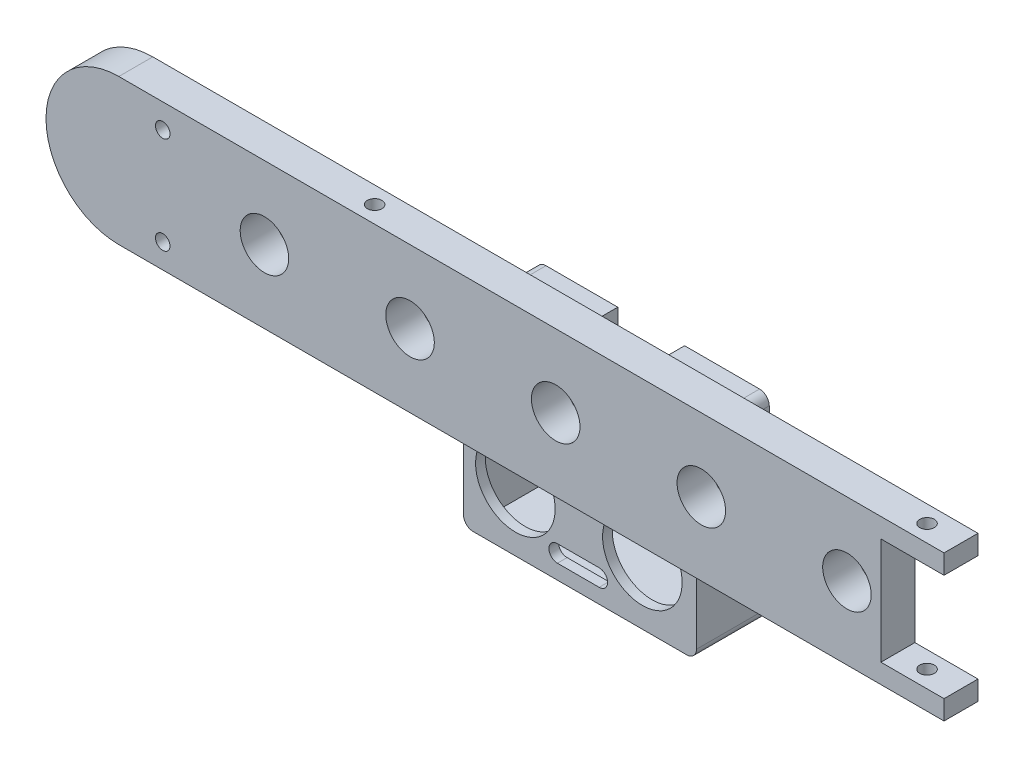
SolidWorks part; units mm, degrees
ref_plane "Front Plane" through (0, 0, 0) normal (0, 0, 1) x (1, 0, 0)
ref_plane "Top Plane" through (0, 0, 0) normal (0, 1, 0) x (1, 0, 0)
ref_plane "Right Plane" through (0, 0, 0) normal (1, 0, 0) x (0, 0, -1)
sketch "Sketch1" plane through (0, 0, 0) normal (0, 0, 1) x (1, 0, 0)
  line L0 (-200, 0) -> (50, 0)
  line L1 (50, -30) -> (-200, -30)
  arc A0 (50, 0) -> (50, -30) centre (50, -15) cw
  arc A1 (-200, -30) -> (-200, 0) centre (-200, -15) cw
  point P7 (-75, 0)
  dimension "D3" = 50
  dimension "D1" = 125
  dimension "D2" = 30
extrude "Boss-Extrude1" add sketch "Sketch1" along normal blind 7
sketch "Sketch2" plane through (0, 0, 7) normal (0, 0, 1) x (1, 0, 0)
  line L2 (50, 0) -> (-200, 0) construction
  circle A0 centre (-185, -15) radius 5
  arc A6 (-200, 0) -> (-200, -30) centre (-200, -15) ccw construction
  point P22 (-215, -15)
  dimension "D1" = 10
  dimension "D3" = 15
  dimension "D2" = 30
extrude "Cut-Extrude1" cut sketch "Sketch2" against normal blind 7
sketch "Sketch5" plane through (0, 0, 0) normal (0, 1, 0) x (1, 0, 0)
  line L1 (-318.748, 64.8797) -> (45.4135, 64.8797) construction
  line L2 (-318.748, 64.8797) -> (-318.748, -30.5338) construction
  line L3 (-318.748, -30.5338) -> (45.4135, -30.5338) construction
  line L4 (45.4135, 64.8797) -> (45.4135, -30.5338) construction
  line L5 (-318.748, 64.8797) -> (45.4135, -30.5338) construction
  line L6 (-318.748, -30.5338) -> (45.4135, 64.8797) construction
  point P0 (-136.6672, 17.1729)
pattern_linear "LPattern1" count 7 spacing 30 along (1, 0, 0) of "Cut-Extrude1"
sketch "Sketch6" plane through (0, 0, 0) normal (0, 0, -1) x (-1, 0, 0)
  circle A0 centre (-50, -15) radius 5
  dimension "D1" = 10
extrude "Cut-Extrude2" cut sketch "Sketch6" against normal blind 10
sketch "Sketch9" plane through (0, 0, 0) normal (0, 0, -1) x (-1, 0, 0)
  line L0 (-50, -15) -> (-29.5, -15)
  line L1 (-29.5, -6.25) -> (-29.5, -23.75)
  circle A0 centre (-29.5, -6.25) radius 1.5
  circle A1 centre (-29.5, -23.75) radius 1.5
  point P6 (-29.5, -15)
  dimension "D3" = 3
  dimension "D4" = 3
  dimension "D1" = 20.5
  dimension "D2" = 17.5
extrude "Cut-Extrude4" cut sketch "Sketch9" against normal up to next contours A1 | A0
sketch "Sketch15" plane through (0, 0, 0) normal (0, 1, 0) x (1, 0, 0)
  line L0 (-200, -7) -> (-200, 0) construction
  line L1 (50, -7) -> (50, 0) construction
  circle A0 centre (-195.8, -3.5) radius 1.5
  circle A1 centre (45.8, -3.5) radius 2.5
  point P7 (-200, -3.5)
  point P12 (50, -3.5)
  dimension "D2" = 3
  dimension "D3" = 5
  dimension "D1" = 4.2
  dimension "D4" = 4.2
extrude "Cut-Extrude9" cut sketch "Sketch15" against normal up to next
sketch "Sketch16" plane through (0, 0, 0) normal (0, 0, -1) x (-1, 0, 0)
  line L0 (153.0436, -46.9176) -> (161.6481, -46.9176) construction
  line L1 (133, -51.6913) -> (181, -51.6913)
  line L2 (133, -51.6913) -> (133, -11.7609)
  line L3 (133, -11.7609) -> (181, -11.7609)
  line L4 (181, -51.6913) -> (181, -11.7609)
  line L9 (153.0436, -45.1752) -> (161.6481, -45.1752)
  line L10 (153.0436, -48.6599) -> (161.6481, -48.6599)
  circle A0 centre (144.1458, -39.2434) radius 8.2
  circle A1 centre (170.3064, -39.2434) radius 8.2
  arc A2 (153.0436, -45.1752) -> (153.0436, -48.6599) centre (153.0436, -46.9176) ccw
  arc A3 (161.6481, -48.6599) -> (161.6481, -45.1752) centre (161.6481, -46.9176) ccw
  circle A4 centre (-50, -15) radius 5 construction
  point P17 (157.3458, -46.9176)
  line M24 (-50, -30) -> (200, -30)
  dimension "D3" = 16.4
  dimension "D4" = 16.4
  dimension "D9" = 11.1458
  dimension "D6" = 8.8978
  dimension "D1" = 48
  dimension "D2" = 26.1606
  dimension "D5" = 8.6044
  dimension "D7" = 11.1458
  dimension "D8" = 11.75
  dimension "D10" = 183
extrude "Boss-Extrude2" add sketch "Sketch16" along normal blind 15 contours A0 M24 | A1 M24 | L10 A3 L9 A2 | L4 L3 L2 L1 region at (-157.3458, -46.9176, 0) region at (-144.1458, -39.2434, 0) region at (-170.3064, -39.2434, 0)
sketch "Sketch17" plane through (0, 0, -15) normal (0, 0, -1) x (-1, 0, 0)
  line L0 (133.75, -20.9008) -> (179.5838, -20.9008)
  line L1 (133.75, -20.9008) -> (133.75, -51.0259)
  line L2 (133.75, -51.0259) -> (179.5838, -51.0259)
  line L3 (179.5838, -20.9008) -> (179.5838, -51.0259)
  line L4 (150.4449, -11.7609) -> (164.2082, -11.7609)
  line L5 (150.4449, -11.7609) -> (150.4449, -20.9835)
  line L6 (150.4449, -20.9835) -> (164.2082, -20.9835)
  line L7 (164.2082, -11.7609) -> (164.2082, -20.9835)
  line L8 (133, -11.7609) -> (181, -11.7609) construction
  circle A0 centre (-50, -15) radius 5 construction
  dimension "D1" = 45.8338
  dimension "D2" = 13.7633
  dimension "D3" = 45.8338
  dimension "D4" = 30.1251
  dimension "D5" = 0
  dimension "D6" = 183.75
  dimension "D7" = 16.6949
extrude "Cut-Extrude15" cut sketch "Sketch17" against normal blind 13 contours L0 L3 L2 L1 | L4 L7 L6 L5
sketch "Sketch18" plane through (0, 0, 7) normal (0, 0, 1) x (1, 0, 0)
  line L1 (65, 42.8797) -> (-75, 42.8797)
  line L2 (65, 42.8797) -> (65, -72.9532)
  line L3 (65, -72.9532) -> (-75, -72.9532)
  line L4 (-75, 42.8797) -> (-75, -72.9532)
  dimension "D1" = 140
extrude "Cut-Extrude16" cut sketch "Sketch18" against normal up to next
fillet "Fillet1" radius 2 4 edges at (-181, -11.7609, -7.5) (-133, -11.7609, -7.5) (-133, -51.6913, -7.5) (-181, -51.6913, -7.5)
sketch "Sketch24" plane through (0, 0, 0) normal (0, 0, -1) x (-1, 0, 0)
  line L1 (200, 0) -> (245, 0)
  line L2 (200, 0) -> (200, -30)
  line L3 (200, -30) -> (245, -30)
  line L4 (245, 0) -> (245, -30)
  arc A0 (245, 0) -> (245, -30) centre (245, -15) cw
  arc M13 (200, -30) -> (200, 0) centre (200, -15) ccw
  dimension "D1" = 45
extrude "Boss-Extrude4" add sketch "Sketch24" against normal blind 7 contours A0 L4 | L4 L1 L3 M13 region at (-228.2218, -15, 0) region at (-251.3662, -15, 0)
sketch "Sketch25" plane through (0, 0, 0) normal (0, 0, -1) x (-1, 0, 0)
  line L0 (235.95, 0) -> (235.95, -30)
  line L1 (75, 0) -> (245, 0) construction
  circle A0 centre (235.95, -25) radius 1.5
  circle A1 centre (235.95, -5) radius 1.5
  arc A2 (245, -30) -> (245, 0) centre (245, -15) ccw construction
  point P9 (260, -15)
  point P10 (235.95, 0)
  dimension "D3" = 3
  dimension "D4" = 3
  dimension "D1" = 30
  dimension "D2" = 20
  dimension "D5" = 5
  dimension "D6" = 24.05
extrude "Cut-Extrude17" cut sketch "Sketch25" against normal blind 10 contours L0 A0 | L0 A0 | L0 A1 | L0 A1 region at (-236.5866, -5, 0) region at (-236.5866, -25, 0) region at (-235.3134, -25, 0) region at (-235.3134, -5, 0)
sketch "Sketch27" plane through (-75, 0, 0) normal (1, 0, 0) x (0, 0, -1)
  line L8 (-7, 0) -> (-7, -30) construction
  line L9 (-7, -4) -> (0, -4)
  line L10 (-7, -4) -> (-7, -26)
  line L11 (-7, -26) -> (0, -26)
  line L12 (0, -4) -> (0, -26)
  line L13 (0, 0) -> (0, -30) construction
  line L14 (-7, -30) -> (0, -30) construction
  line L15 (0, 0) -> (-7, 0) construction
  dimension "D1" = 4
  dimension "D2" = 4
extrude "Cut-Extrude18" cut sketch "Sketch27" against normal blind 13
sketch "Sketch28" plane through (0, 0, 0) normal (0, 1, 0) x (1, 0, 0)
  line L0 (-75, 0) -> (-75, -7) construction
  circle A0 centre (-82, -3.5) radius 1.5
  dimension "D2" = 3
  dimension "D1" = 7
extrude "Cut-Extrude19" cut sketch "Sketch28" against normal through all both and the other way through all
sketch "Sketch29" plane through (0, 0, 0) normal (0, 0, -1) x (-1, 0, 0)
  line L0 (245, -30) -> (181, -30) construction
  circle A0 centre (215, -15) radius 5
  arc A2 (245, -30) -> (245, 0) centre (245, -15) ccw construction
  dimension "D1" = 10
  dimension "D2" = 15
  dimension "D3" = 30
extrude "Cut-Extrude20" cut sketch "Sketch29" against normal through all both and the other way through all
